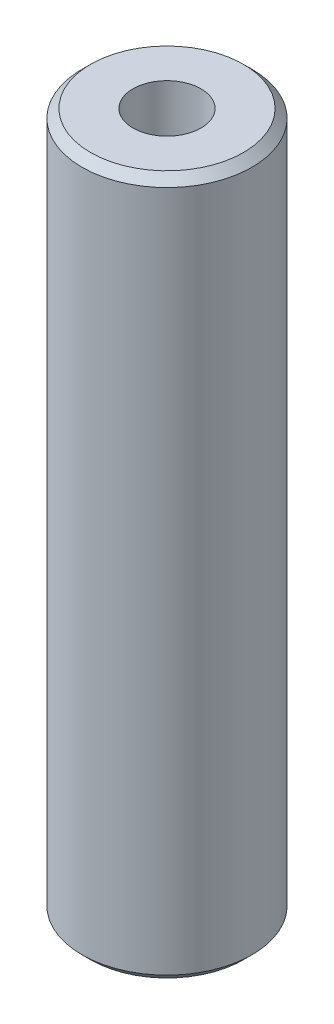
SolidWorks part; units mm, degrees
ref_plane "Front Plane" through (0, 0, 0) normal (0, 0, 1) x (1, 0, 0)
ref_plane "Top Plane" through (0, 0, 0) normal (0, 1, 0) x (1, 0, 0)
ref_plane "Right Plane" through (0, 0, 0) normal (1, 0, 0) x (0, 0, -1)
sketch "Sketch1" plane through (0, 0, 0) normal (0, 1, 0) x (1, 0, 0)
  circle A0 centre (0, 0) radius 40
  dimension "SHAFT_OD" = 80
extrude "Boss-Extrude1" add sketch "Sketch1" along normal blind 329.1328
sketch "Sketch2" plane through (0, 0, 0) normal (0, 1, 0) x (1, 0, 0)
  circle A0 centre (0, 0) radius 16.0208
  dimension "BORE_D" = 32.0416
extrude "Cut-Extrude1" cut sketch "Sketch2" along normal through all
chamfer "Chamfer1" distance 4.0051 angle 45 2 edges at (0, 329.1328, 40) (0, 0, 40)
